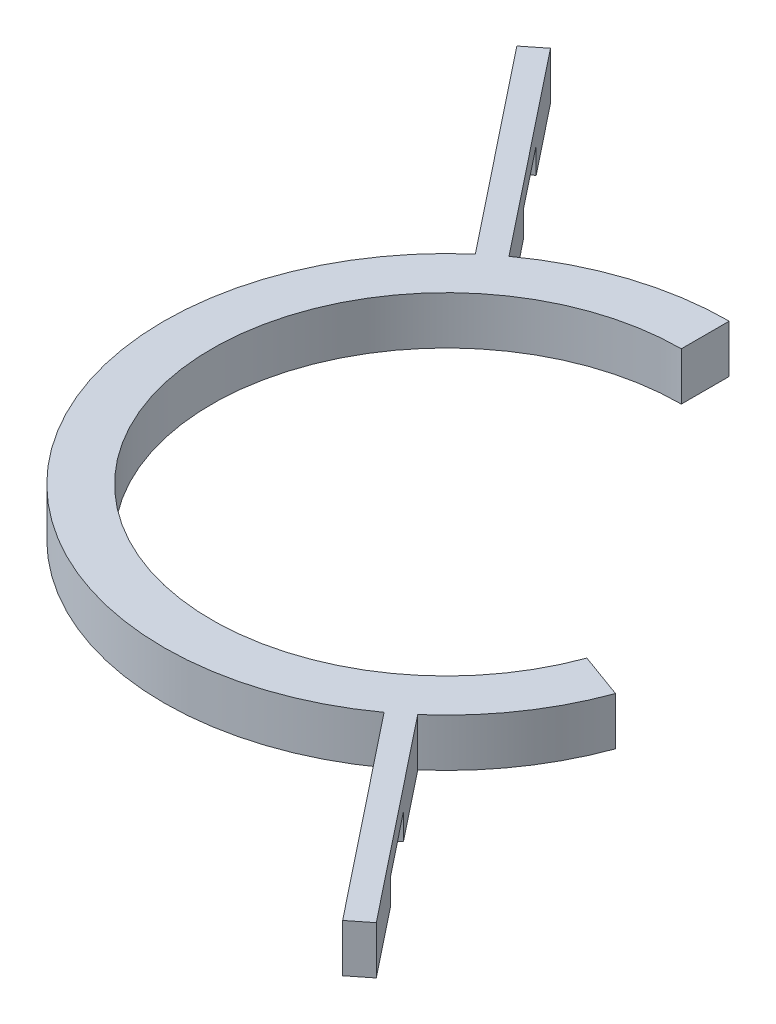
SolidWorks part; units mm, degrees
ref_plane "Front Plane" through (0, 0, 0) normal (0, 0, 1) x (1, 0, 0)
ref_plane "Top Plane" through (0, 0, 0) normal (0, 1, 0) x (1, 0, 0)
ref_plane "Right Plane" through (0, 0, 0) normal (1, 0, 0) x (0, 0, -1)
sketch "Sketch1" plane through (0, 0, 0) normal (0, 1, 0) x (1, 0, 0)
  line L0 (0, 4.9) -> (0, 5.9)
  line L1 (4.6045, -1.6759) -> (5.5442, -2.0179)
  line L2 (-6.2169, 7.8327) -> (6.2169, -7.8327)
  line L3 (3.0678, -4.2672) -> (6.7979, -8.9668)
  line L4 (3.4594, -3.9564) -> (7.1895, -8.656)
  line L5 (6.7979, -8.9668) -> (7.1895, -8.656)
  line L6 (-3.4594, 3.9564) -> (-7.1895, 8.656)
  line L7 (-3.0678, 4.2672) -> (-6.7979, 8.9668)
  line L8 (-6.7979, 8.9668) -> (-7.1895, 8.656)
  line L9 (-5.4474, -4.3237) -> (5.4474, 4.3237)
  circle A0 centre (0, 0) radius 5.9
  circle A1 centre (0, 0) radius 4.9
  point P11 (0, 0)
  point P13 (-5.3492, 0.0934)
  point P15 (-4.3493, 0.0759)
  point P18 (3.0678, -4.2672)
  point P19 (0, 0)
  point P26 (-0.0247, 0.0404)
  point P27 (0, 0)
  point P30 (0, 0)
  dimension "D1" = 1
  dimension "D3" = 11.8
  dimension "D2" = 110
  dimension "D4" = 2
  dimension "D5" = 0.5
extrude "Boss-Extrude2" add sketch "Sketch1" along normal blind 1 contours A1 L9 A0 L2 | A1 L2 A0 L9 | A0 L7 L8 L6 | A1 L0 A0 L2 | A1 L2 A0 L1 | A0 L3 L5 L4 region at (-1.7495, 0, -5.0182) region at (-4.955, 0, -0.5699) region at (-3.6045, 0, -4.7445) region at (-0.5699, 0, 4.955) region at (4.338, 0, 3.1264) region at (3.8023, 0, 4.5875)
sketch "Sketch2" plane through (-0.1958, 0, 0.1554) normal (-0.7833, 0, 0.6217) x (0.6217, 0, 0.7833)
  line L0 (8.5721, 1) -> (8.5721, 0) construction
  line L1 (5.8947, 1) -> (11.2496, 1) construction
  line L2 (5.8947, 0) -> (11.2496, 0) construction
  line L3 (7.7427, 0) -> (7.7427, 0.5415)
  line L4 (7.7427, 0.5415) -> (9.4016, 0.5415)
  line L5 (9.4016, 0.5415) -> (9.4016, 0)
  line L6 (7.7427, 0) -> (9.4016, 0)
  line L8 (0, 0) -> (0, 4.985) construction
  line L11 (-7.7427, 0) -> (-7.7427, 0.5415)
  line L12 (-7.7427, 0.5415) -> (-9.4016, 0.5415)
  line L13 (-9.4016, 0.5415) -> (-9.4016, 0)
  line L14 (-7.7427, 0) -> (-9.4016, 0)
  point P17 (0, 0)
extrude "Cut-Extrude2" cut sketch "Sketch2" against normal blind 1
